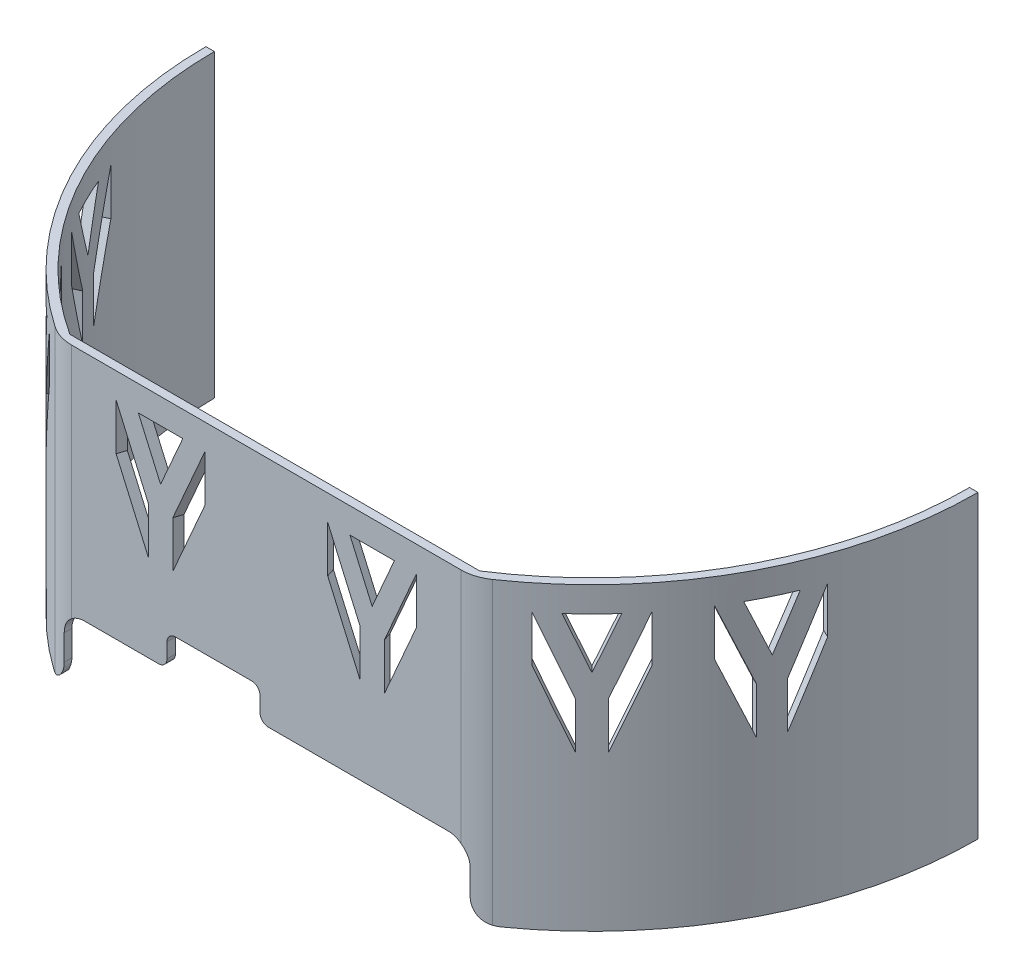
SolidWorks part; units mm, degrees
ref_plane "Front Plane" through (0, 0, 0) normal (0, 0, 1) x (1, 0, 0)
ref_plane "Top Plane" through (0, 0, 0) normal (0, 1, 0) x (1, 0, 0)
ref_plane "Right Plane" through (0, 0, 0) normal (1, 0, 0) x (0, 0, -1)
sketch "Sketch1" plane through (0, 0, 0) normal (0, 1, 0) x (1, 0, 0)
  line L0 (0, 124.168) -> (0, -125.7458) construction
  line L1 (-136.0011, 0) -> (148.623, 0) construction
  line L2 (-48.4715, -75) -> (48.4715, -75)
  line L3 (-49.058, -77) -> (49.058, -77)
  arc A0 (48.4715, -75) -> (-48.4715, -75) centre (0, 0) ccw
  arc A1 (49.058, -77) -> (-49.058, -77) centre (0, 0) ccw
  dimension "D1" = 178.6
  dimension "D3" = 182.6
  dimension "D2" = 75
  dimension "D4" = 77
extrude "Boss-Extrude1" add sketch "Sketch1" along normal blind 71
fillet "Fillet1" radius 10 2 edges at (-49.058, 35.5, 77) (49.058, 35.5, 77)
sketch "Sketch2" plane through (0, 0, 77) normal (0, 0, 1) x (1, 0, 0)
  line L0 (0, 94.4811) -> (0, -36.6428) construction
  line L1 (46.051, 0) -> (51.7153, 0) construction
  line L2 (-48, 16) -> (48, 16)
  line L4 (-48, 16) -> (-48, 0)
  line L5 (-48, 0) -> (48, 0)
  line L6 (48, 16) -> (48, 0)
  line L7 (-48, 16) -> (48, 0) construction
  line L8 (-48, 0) -> (48, 16) construction
  line L9 (-46.051, 71) -> (46.051, 71) construction
  point P3 (0, 8)
  dimension "D1" = 55
  dimension "D2" = 96
extrude "Cut-Extrude1" cut sketch "Sketch2" against normal blind 5
sketch "Sketch3" plane through (0, 0, 77) normal (0, 0, 1) x (1, 0, 0)
  line L0 (0, 94.4811) -> (0, -26.607) construction
  line L1 (46.051, 16) -> (-46.051, 16) construction
  line L2 (-23.5, 16) -> (-1.5, 16)
  line L3 (-23.5, 16) -> (-23.5, 23.5)
  line L4 (-23.5, 23.5) -> (-1.5, 23.5)
  line L5 (-1.5, 16) -> (-1.5, 23.5)
  dimension "D1" = 22
  dimension "D2" = 7.5
  dimension "D3" = 1.5
extrude "Cut-Extrude2" cut sketch "Sketch3" against normal blind 5
fillet "Fillet2" radius 5 4 edges at (-48, 16, 75.9041) (-48, 0, 75.9041) (48, 16, 75.9041) (48, 0, 75.9041)
fillet "Fillet3" radius 2 4 edges at (-1.5, 16, 76) (-1.5, 23.5, 76) (-23.5, 16, 76) (-23.5, 23.5, 76)
sketch "Sketch4" plane through (0, 0, 0) normal (0, 0, 1) x (1, 0, 0)
  line L0 (0, 103.2008) -> (0, -37.4655) construction
  line L1 (-5, 65) -> (5, 65)
  line L2 (-5, 65) -> (0, 53)
  line L3 (0, 53) -> (5, 65)
  line L8 (-46.051, 71) -> (46.051, 71) construction
  line L9 (-10, 65) -> (-2.75, 47.6)
  line L10 (-2.75, 47.6) -> (-2.75, 36.6)
  line L11 (-2.75, 36.6) -> (-10, 54)
  line L12 (-10, 54) -> (-10, 65)
  line L13 (10, 65) -> (2.75, 47.6)
  line L14 (2.75, 47.6) -> (2.75, 36.6)
  line L15 (2.75, 36.6) -> (10, 54)
  line L16 (10, 54) -> (10, 65)
  point P6 (0, 65)
  dimension "D1" = 10
  dimension "D2" = 6
  dimension "D3" = 5
  dimension "D4" = 11
  dimension "D5" = 12
  dimension "D6" = 2.75
extrude "Cut-Extrude3" cut sketch "Sketch4" against normal blind 132
pattern_circular "CirPattern1" count 20 over 360 about axis through (0, 71, 0) along (0, 1, 0) skipping 1, 2, 3, 4, 5, 6, 7, 8, 10, 12, 13, 14, 15, 16, 17, 18, 19 of "Cut-Extrude3"
pattern_circular "CirPattern2" count 16 over 360 about axis through (0, 71, 0) along (0, 1, 0) skipping 1, 2, 3, 4, 5, 7, 8, 9, 11, 12, 13, 14, 15 of "Cut-Extrude3"
pattern_circular "CirPattern3" count 28 over 360 about axis through (0, 71, 0) along (0, 1, 0) skipping 1, 2, 3, 4, 5, 6, 7, 8, 10, 11, 12, 13, 14, 15, 16, 17, 18, 20, 21, 22, 23, 24, 25, 26, 27 of "Cut-Extrude3"
sketch "Sketch5" plane through (0, 0, 77) normal (0, 0, 1) x (1, 0, 0)
  line L0 (0, 101.7201) -> (0, -38.7816) construction
  line L1 (-5, 65) -> (5, 65)
  line L2 (-5, 65) -> (0, 53)
  line L3 (0, 53) -> (5, 65)
  line L4 (-10, 65) -> (-2.75, 47.6)
  line L5 (-2.75, 47.6) -> (-2.75, 36.6)
  line L6 (-2.75, 36.6) -> (-10, 54)
  line L7 (-10, 54) -> (-10, 65)
  line L8 (-46.051, 71) -> (46.051, 71) construction
  line L9 (10, 65) -> (2.75, 47.6)
  line L10 (2.75, 47.6) -> (2.75, 36.6)
  line L11 (2.75, 36.6) -> (10, 54)
  line L12 (10, 54) -> (10, 65)
  point P6 (0, 65)
  dimension "D1" = 10
  dimension "D2" = 5
  dimension "D3" = 11
  dimension "D4" = 2.75
  dimension "D5" = 28.4
  dimension "D6" = 6
  dimension "D7" = 5
  dimension "D8" = 2.75
  dimension "D9" = 12
extrude "Boss-Extrude2" add sketch "Sketch5" against normal blind 5
sketch "Sketch6" plane through (0, 0, 0) normal (0, 1, 0) x (1, 0, 0)
  line L0 (-100.8658, 0) -> (109.8927, 0) construction
  line L1 (-46.051, -77) -> (46.051, -77) construction
  line L3 (-100.8658, 0) -> (109.8927, 0)
  line L4 (-100.8658, 0) -> (-100.8658, 95.751)
  line L5 (-100.8658, 95.751) -> (109.8927, 95.751)
  line L6 (109.8927, 0) -> (109.8927, 95.751)
  dimension "D1" = 77
extrude "Cut-Extrude4" cut sketch "Sketch6" along normal blind 92
ref_plane "Plane1" through (89.3, 0, 0) normal (-1, 0, 0) x (0, 0, 1)
ref_plane "Plane2" through (-89.3, 0, 0) normal (1, 0, 0) x (0, 0, -1)
equation "\"D5@Sketch4\"=20-\"D2@Sketch4\"-2"
equation "\"D9@Sketch5\"=20-\"D6@Sketch5\"-2"
